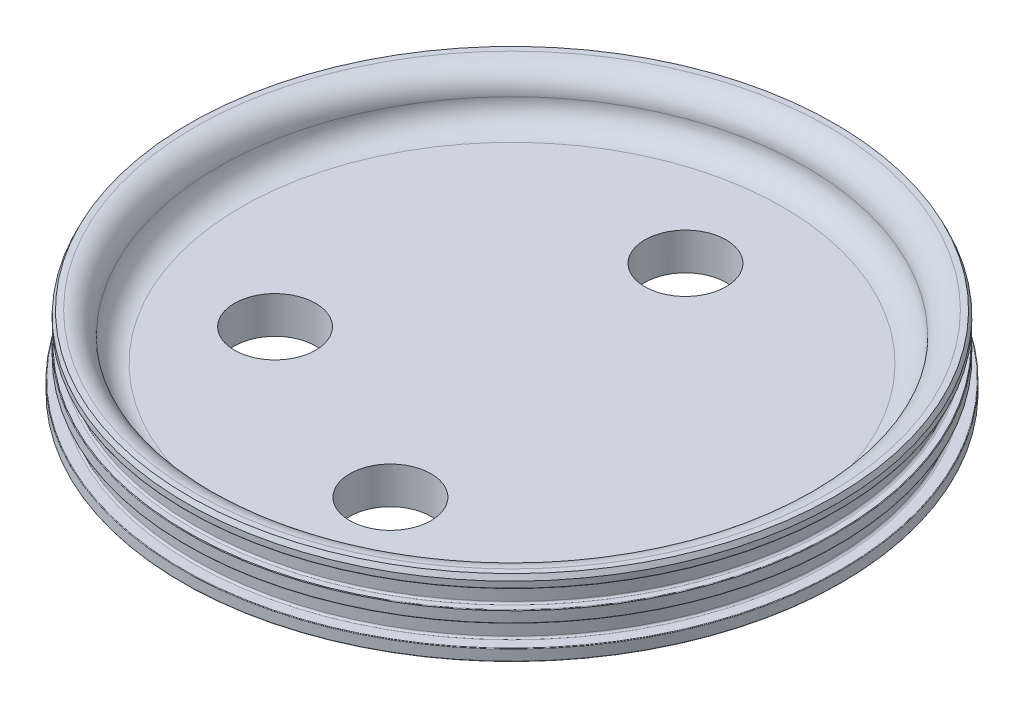
SolidWorks part; units mm, degrees
material "6061-T6 (SS)"
ref_plane "Front Plane" through (0, 0, 0) normal (0, 0, 1) x (1, 0, 0)
ref_plane "Top Plane" through (0, 0, 0) normal (0, 1, 0) x (1, 0, 0)
ref_plane "Right Plane" through (0, 0, 0) normal (1, 0, 0) x (0, 0, -1)
sketch "Sketch1" plane through (0, 0, 0) normal (0, 0, 1) x (1, 0, 0)
  line L0 (0, 48.1922) -> (0, -25.6743) construction
  line L1 (0, 0) -> (72.39, 0)
  line L2 (72.39, 0) -> (72.39, 2.54)
  line L3 (72.39, 2.54) -> (69.6468, 2.54)
  line L4 (69.6468, 2.54) -> (69.6468, 6.604)
  line L5 (69.6468, 6.604) -> (71.4248, 6.604)
  line L6 (71.4248, 6.604) -> (71.4248, 9.144)
  line L7 (71.4248, 9.144) -> (69.6468, 9.144)
  line L8 (64.5668, 15.748) -> (64.5668, 5.588)
  line L9 (64.5668, 5.588) -> (0, 5.588)
  line L10 (0, 5.588) -> (0, 0)
  line L11 (69.6468, 9.144) -> (69.6468, 13.208)
  line L12 (69.6468, 13.208) -> (71.4248, 13.208)
  line L13 (71.4248, 13.208) -> (71.4248, 15.748)
  line L14 (71.4248, 15.748) -> (64.5668, 15.748)
  dimension "D2" = 4.064
  dimension "D5" = 5.588
  dimension "D7" = 4.064
  dimension "D3" = 2.54
  dimension "D4" = 2.54
  dimension "D8" = 5.08
  dimension "D9" = 10.16
  dimension "D1" = 72.39
  dimension "D10" = 1.778
  dimension "D6" = 69.6468
revolve "Revolve1" add sketch "Sketch1" angle 360 about L0
sketch "Sketch6" plane through (0, 0, 0) normal (0, -1, 0) x (1, 0, 0)
  circle A0 centre (0, 0) radius 66.04
  dimension "D1" = 132.08
extrude "Boss-Extrude1" add sketch "Sketch6" along normal blind 2.54
fillet "CNC ID Fillet" radius 0.4064 5 edges at (-69.6468, 6.604, 0) (-69.6468, 2.54, 0) (66.04, 0, 0) (-69.6468, 13.208, 0) (-69.6468, 9.144, 0)
fillet "CNC OD Fillet" radius 0.127 6 edges at (-71.4248, 6.604, 0) (-72.39, 2.54, 0) (-71.4248, 9.144, 0) (-71.4248, 13.208, 0) (66.04, -2.54, 0) (-72.39, 0, 0)
chamfer "CNC Chamfers" distance 0.508 angle 65 1 edges at (-71.4248, 15.748, 0) first distance on face at (-64.5668, 15.748, 0)
hole_wizard "Pipe Tap Drill for 1/2 Tap - Fill Valve" positions "Sketch13" profile "Sketch14" hole size "1/2" standard "ANSI Inch" end condition through all
sketch "Sketch13" plane through (0, -2.54, 0) normal (0, -1, 0) x (-1, 0, 0)
  point P4 (0, 38.1)
  dimension "D1" = 38.1
sketch "Sketch14" plane through (0, -2.54, -38.1) normal (1, 0, 0) x (0, 0, -1)
  line L0 (0, 0) -> (0, 18.288)
  line L1 (0, 18.288) -> (8.9281, 18.288)
  line L2 (8.9281, 18.288) -> (8.9281, 0)
  line L5 (8.9281, 0) -> (0, 0)
  line L11 (0, -6.35) -> (0, 107.95) construction
  dimension "Thru Hole Dia." = 17.8562
  dimension "Thru Hole Depth" = 18.288
hole_wizard "Pipe Tap Drill for 1/4 Tap - Solenoid Valve" positions "Sketch15" profile "Sketch16" hole size "1/2" standard "ANSI Inch" end condition through all
sketch "Sketch15" plane through (0, -2.54, 0) normal (0, -1, 0) x (-1, 0, 0)
  line L2 (-12.0892, -38.8003) -> (0, 0) construction
  line L3 (0, 0) -> (0, -38.8003) construction
  point P4 (-12.0892, -38.8003)
  dimension "D1" = 17.306
  dimension "D2" = 40.64
  dimension "D3" = 38.8003
sketch "Sketch16" plane through (12.0892, -2.54, 38.8003) normal (1, 0, 0) x (0, 0, -1)
  line L0 (0, 0) -> (0, 18.288)
  line L1 (0, 18.288) -> (8.9281, 18.288)
  line L2 (8.9281, 18.288) -> (8.9281, 0)
  line L5 (8.9281, 0) -> (0, 0)
  line L11 (0, -6.35) -> (0, 107.95) construction
  dimension "Thru Hole Dia." = 17.8562
  dimension "Thru Hole Depth" = 18.288
hole_wizard "Pipe Tap Drill for 1/2 Tap - Cryo Valve" positions "Sketch17" profile "Sketch18" hole size "1/2" standard "ANSI Inch" end condition through all
sketch "Sketch17" plane through (0, -2.54, 0) normal (0, -1, 0) x (-1, 0, 0)
  line L0 (32.9956, -19.05) -> (17.2813, -19.05) construction
  line L2 (32.9956, -19.05) -> (0, 0) construction
  point P4 (32.9956, -19.05)
  dimension "D1" = 30
  dimension "D2" = 38.1
sketch "Sketch18" plane through (-32.9956, -2.54, 19.05) normal (1, 0, 0) x (0, 0, -1)
  line L0 (0, 0) -> (0, 18.288)
  line L1 (0, 18.288) -> (8.9281, 18.288)
  line L2 (8.9281, 18.288) -> (8.9281, 0)
  line L5 (8.9281, 0) -> (0, 0)
  line L11 (0, -6.35) -> (0, 107.95) construction
  dimension "Thru Hole Dia." = 17.8562
  dimension "Thru Hole Depth" = 18.288
fillet "Fillet1" radius 5.08 2 edges at (-64.5668, 5.588, 0) (-64.5668, 15.748, 0)
equation "\"D6@Sketch1\"=5.484/2"
equation "\"D1@Sketch1\"=5.7/2"
